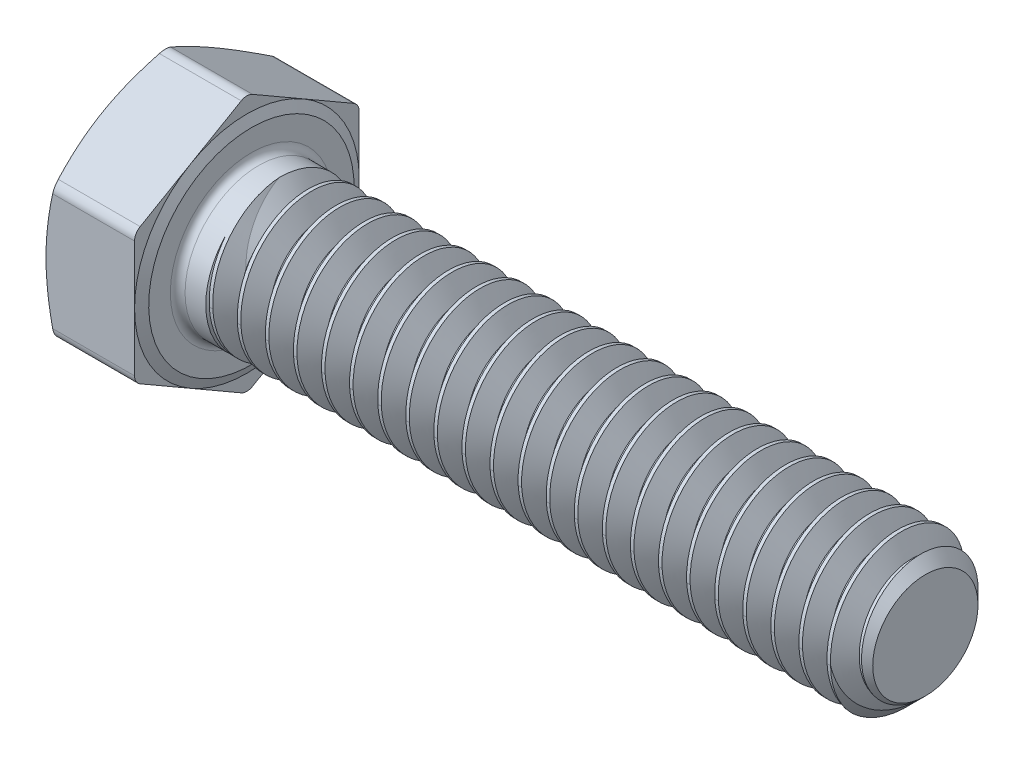
SolidWorks part; units mm, degrees
ref_plane "Front Plane" through (0, 0, 0) normal (0, 0, 1) x (1, 0, 0)
ref_plane "Top Plane" through (0, 0, 0) normal (0, 1, 0) x (1, 0, 0)
ref_plane "Right Plane" through (0, 0, 0) normal (1, 0, 0) x (0, 0, -1)
sketch "Sketch1" plane through (0, 0, 0) normal (0, 0, 1) x (1, 0, 0)
  line L0 (0, 0) -> (19.05, 0) construction
  line L1 (0, 0) -> (-2.7781, 0) construction
  line L2 (0, 3.175) -> (0, -3.175) construction
  line L3 (-2.7781, 3.175) -> (-2.7781, -3.175) construction
  line L4 (19.05, 2.0828) -> (19.05, -2.0828) construction
  line L8 (18.2563, 2.0828) -> (19.05, 2.0828) construction
  point P8 (18.2563, 0)
  point P11 (16.2719, -2.0828)
  point P12 (0.7937, 0)
  dimension "Head Height" = 2.7781
  dimension "Head Width" = 6.35
  dimension "Length" = 19.05
  dimension "Thread Size" = 4.1656
  dimension "D1" = 2.7781
  dimension "Thread Pitch" = 0.7937
  dimension "D2" = 0.7937
sketch "Sketch2" plane through (0, 0, 0) normal (1, 0, 0) x (0, 0, -1)
  circle A0 centre (0, 0) radius 2.0828
extrude "Boss-Extrude1" add sketch "Sketch2" along normal up to vertex (19.05 mm away) up to point (19.05, 2.0828, 0)
sketch "Sketch3" plane through (0, 0, 0) normal (-1, 0, 0) x (0, 0, 1)
  line L0 (0, 3.6662) -> (0, 0) construction
  line L1 (0, 3.6662) -> (-3.175, 1.8331)
  line L2 (-3.175, 1.8331) -> (-3.175, -1.8331)
  line L3 (-3.175, -1.8331) -> (0, -3.6662)
  line L4 (0, -3.6662) -> (3.175, -1.8331)
  line L5 (3.175, -1.8331) -> (3.175, 1.8331)
  line L6 (3.175, 1.8331) -> (0, 3.6662)
  circle A0 centre (0, 0) radius 3.175 construction
extrude "Boss-Extrude2" add sketch "Sketch3" along normal up to vertex (2.7781 mm away) up to point (-2.7781, 3.175, 0)
sketch "Sketch5" plane through (-2.7781, 0, 0) normal (-1, 0, 0) x (0, 0, 1)
  circle A0 centre (0, 0) radius 3.175 construction
  circle A1 centre (0, 0) radius 3.175 construction
  circle A2 centre (0, 0) radius 2.8575
  dimension "D1" = 0.3175
extrude "Cut-Extrude1" cut sketch "Sketch5" against normal up to vertex (2.7781 mm away) draft 65 flip side to cut up to point (0, 0, 0)
sketch "Sketch11" plane through (-2.7781, 0, 0) normal (-1, 0, 0) x (0, 0, 1)
  line L0 (0, 2.2543) -> (0, 1.397) construction
  line L1 (0.127, 2.2543) -> (0.127, 1.397)
  line L2 (-0.127, 2.2543) -> (-0.127, 1.397)
  arc A0 (0.127, 2.2543) -> (-0.127, 2.2543) centre (0, 2.2543) ccw
  arc A1 (-0.127, 1.397) -> (0.127, 1.397) centre (0, 1.397) ccw
  circle A2 centre (0, 0) radius 2.3813 construction
  circle A3 centre (0, 0) radius 1.27 construction
  point P3 (0, 1.8256)
  dimension "D1" = 4.7625
  dimension "D3" = 0.254
extrude "Boss-Extrude5" add sketch "Sketch11" along normal blind 0.0635
fillet "Fillet5" radius 0.0635 4 edges at (-2.8416, 1.8256, 0.127) (-2.8416, 1.27, 0) (-2.8416, 1.8256, -0.127) (-2.8416, 2.3813, 0)
pattern_circular "CirPattern1" count 6 over 360 about axis through (0, 0, 0) along (-1, 0, 0) of "Boss-Extrude5", "Fillet5" reverse direction yes
fillet "Fillet7" radius 0.3175 6 edges at (-1.2005, -3.6662, 0) (-1.2005, -1.8331, -3.175) (-1.2005, 1.8331, -3.175) (-1.2005, 3.6662, 0) (-1.2005, -1.8331, 3.175) (-1.2005, 1.8331, 3.175)
chamfer "Chamfer1" distance 0.5953 angle 45 1 edges at (19.05, 0, -2.0828)
sketch "Sketch15" plane through (0, 0, 0) normal (0, 0, 1) x (1, 0, 0)
  line L0 (0, 2.9026) -> (-0.127, 3.175)
  line L1 (0, 3.175) -> (0, -3.175) construction
  line L2 (-0.127, 3.175) -> (-0.127, 3.6662)
  line L3 (-0.127, 3.6662) -> (0, 3.6662)
  line L4 (0, 3.6662) -> (0, 2.9026)
  dimension "D1" = 0.127
  dimension "D2" = 25
revolve "Cut-Revolve1" cut sketch "Sketch15" angle 360 about L1
fillet "Fillet4" radius 0.2083 1 edges at (0, 0, 2.0828)
sketch "Reference Sketch1" plane through (0, 0, 0) normal (1, 0, 0) x (0, 0, -1)
  line L1 (0, 3.6662) -> (-3.175, 1.8331)
  line L2 (-3.175, 1.8331) -> (-3.175, -1.8331)
  line L3 (-3.175, -1.8331) -> (0, -3.6662)
  line L4 (0, -3.6662) -> (3.175, -1.8331)
  line L5 (3.175, -1.8331) -> (3.175, 1.8331)
  line L6 (3.175, 1.8331) -> (0, 3.6662)
  circle A0 centre (0, 0) radius 3.175 construction
  circle A1 centre (0, 0) radius 3.175
sketch "Sketch12" plane through (19.05, 0, 0) normal (1, 0, 0) x (0, 0, -1)
  circle A1 centre (0, 0) radius 2.0828
ref_plane "Plane2" through (0.7937, 0, 0) normal (1, 0, 0) x (0, 0, -1)
split "Split1" trim tools "Plane2" bodies to split 126 116 resulting bodies 118 119
curve "Helix/Spiral2" pitch 0.7937 height 19.8438 radius 2.0828 centre (19.05, 0, 0) axis (-1, 0, 0) start towards (0, 1, 0) parameters "Pitch"=0.7937
sketch "Sketch13" plane through (0, 0, 0) normal (0, 0, 1) x (1, 0, 0)
  line L0 (19.0004, 2.1687) -> (19.3973, 1.4813) construction
  line L1 (19.3973, 1.4813) -> (19.7941, 2.1687) construction
  line L2 (19.7941, 2.1687) -> (19.0004, 2.1687) construction
  line L3 (19.3973, 1.4813) -> (19.3973, 1.5672) construction
  line L4 (19.05, 2.0828) -> (19.7445, 2.0828)
  line L5 (19.3973, 2.0828) -> (19.3973, 2.1687) construction
  line L6 (19.7445, 2.0828) -> (19.4469, 1.5672)
  line L7 (19.4469, 1.5672) -> (19.3477, 1.5672)
  line L8 (19.3477, 1.5672) -> (19.05, 2.0828)
  line L9 (18.2563, 2.0828) -> (19.05, 2.0828) construction
  dimension "D1" = 0.0992
sweep "Cut-Sweep1" cut profiles "Sketch13" path "Helix/Spiral2" align with end faces yes
sketch "Sketch14" plane through (0.7937, 0, 0) normal (1, 0, 0) x (0, 0, -1)
  circle A1 centre (0, 0) radius 2.0828
  circle A2 centre (0, 0) radius 2.0828
  dimension "D1" = 0
extrude "Boss-Extrude4" add sketch "Sketch14" along normal through all draft 50
equation "\"D1@Sketch11\"=\"Head Width@Sketch1\" * 0.75"
equation "\"D2@Sketch11\"=\"Head Width@Sketch1\"*0.4"
equation "\"D3@Sketch11\"=\"Head Width@Sketch1\" * .04"
equation "\"D3@Helix/Spiral2\"=\"Length@Sketch1\" + \"Thread Pitch@Sketch1\""
equation "\"D1@Chamfer1\"=\"Thread Pitch@Sketch1\"*0.750"
equation "\"D1@Sketch1\"=\"Thread Pitch@Sketch1\"*3.5"
equation "\"Pitch@Helix/Spiral2\"=\"Thread Pitch@Sketch1\""
equation "\"D1@Sketch13\"=\"Thread Pitch@Sketch1\"*0.125"
equation "\"D1@Sketch5\"=\"Head Width@Sketch1\"*0.05"
equation "\"D1@Fillet4\"=\"Thread Size@Sketch1\"*0.05"
equation "\"D2@Sketch1\"=\"Thread Pitch@Sketch1\""
equation "\"D1@Fillet7\"=\"Head Width@Sketch1\"*0.05"
